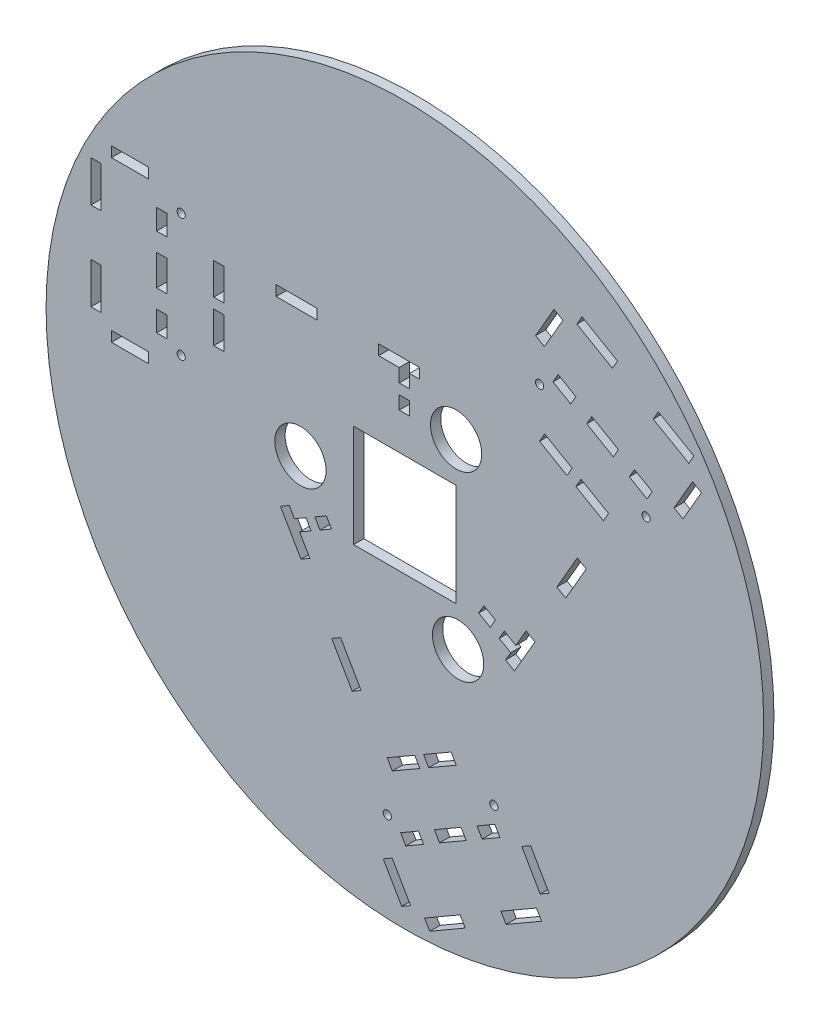
SolidWorks part; units mm, degrees
material "Balsa"
ref_plane "Plan de face" through (0, 0, 0) normal (0, 0, 1) x (1, 0, 0)
ref_plane "Plan de dessus" through (0, 0, 0) normal (0, 1, 0) x (1, 0, 0)
ref_plane "Plan de droite" through (0, 0, 0) normal (1, 0, 0) x (0, 0, -1)
sketch "Esquisse1" plane through (0, 0, 0) normal (0, 0, 1) x (1, 0, 0)
  circle A0 centre (148.0804, -12.1102) radius 175
  dimension "D1" = 350
extrude "Boss.-Extru.1" add sketch "Esquisse1" along normal blind 5
sketch "Esquisse2" plane through (0, 0, 5) normal (0, 0, 1) x (1, 0, 0)
  line L0 (135.3118, 53.7774) -> (135.3118, 48.7774)
  line L1 (5, 72.2774) -> (23, 72.2774)
  line L2 (5, 72.2774) -> (5, 67.2774)
  line L3 (5, 67.2774) -> (23, 67.2774)
  line L4 (23, 72.2774) -> (23, 67.2774)
  line L5 (-5, 62.2774) -> (0, 62.2774)
  line L6 (-5, 62.2774) -> (-5, 42.2774)
  line L7 (-5, 42.2774) -> (0, 42.2774)
  line L8 (0, 62.2774) -> (0, 42.2774)
  line L9 (-5, 19.2774) -> (0, 19.2774)
  line L10 (-5, 19.2774) -> (-5, -0.7226)
  line L11 (-5, -0.7226) -> (0, -0.7226)
  line L12 (0, 19.2774) -> (0, -0.7226)
  line L13 (5, -5.7226) -> (23, -5.7226)
  line L14 (5, -5.7226) -> (5, -10.7226)
  line L15 (5, -10.7226) -> (23, -10.7226)
  line L16 (23, -5.7226) -> (23, -10.7226)
  line L17 (27, 14.2774) -> (32, 14.2774)
  line L18 (27, 14.2774) -> (27, 4.2774)
  line L19 (27, 4.2774) -> (32, 4.2774)
  line L20 (32, 14.2774) -> (32, 4.2774)
  line L21 (27, 38.2774) -> (32, 38.2774)
  line L22 (27, 38.2774) -> (27, 23.2774)
  line L23 (27, 23.2774) -> (32, 23.2774)
  line L24 (32, 38.2774) -> (32, 23.2774)
  line L25 (27, 57.2774) -> (32, 57.2774)
  line L26 (27, 57.2774) -> (27, 47.2774)
  line L27 (27, 47.2774) -> (32, 47.2774)
  line L28 (32, 57.2774) -> (32, 47.2774)
  line L29 (54.86, 48.7774) -> (59.86, 48.7774)
  line L30 (54.86, 48.7774) -> (54.86, 33.2774)
  line L31 (54.86, 33.2774) -> (59.86, 33.2774)
  line L32 (59.86, 48.7774) -> (59.86, 33.2774)
  line L33 (54.86, 28.2774) -> (59.86, 28.2774)
  line L34 (54.86, 28.2774) -> (54.86, 12.7774)
  line L35 (54.86, 12.7774) -> (59.86, 12.7774)
  line L36 (59.86, 28.2774) -> (59.86, 12.7774)
  line L37 (85.3118, 53.7774) -> (105.3118, 53.7774)
  line L38 (85.3118, 53.7774) -> (85.3118, 48.7774)
  line L39 (85.3118, 48.7774) -> (105.3118, 48.7774)
  line L40 (105.3118, 53.7774) -> (105.3118, 48.7774)
  line L41 (145.3118, 37.2774) -> (150.3118, 37.2774)
  line L42 (145.3118, 37.2774) -> (145.3118, 30.7774)
  line L43 (145.3118, 30.7774) -> (150.3118, 30.7774)
  line L44 (150.3118, 37.2774) -> (150.3118, 30.7774)
  line L45 (135.3118, 48.7774) -> (145.3118, 48.7774)
  line L46 (155.3118, 48.7774) -> (135.3118, 48.7774) construction
  line L47 (145.3118, 48.7774) -> (145.3118, 42.2774)
  line L48 (145.3118, 42.2774) -> (150.3118, 42.2774)
  line L49 (150.3118, 42.2774) -> (150.3118, 48.7774)
  line L50 (150.3118, 48.7774) -> (155.3118, 48.7774)
  line L51 (155.3118, 48.7774) -> (155.3118, 53.7774)
  line L52 (155.3118, 53.7774) -> (135.3118, 53.7774)
  line L53 (292.7025, 69.6073) -> (283.7025, 54.0188)
  line L54 (292.7025, 69.6073) -> (288.3723, 72.1073)
  line L55 (288.3723, 72.1073) -> (279.3723, 56.5188)
  line L56 (283.7025, 54.0188) -> (279.3723, 56.5188)
  line L57 (289.0422, 83.2676) -> (286.5422, 78.9374)
  line L58 (289.0422, 83.2676) -> (271.7217, 93.2676)
  line L59 (271.7217, 93.2676) -> (269.2217, 88.9374)
  line L60 (286.5422, 78.9374) -> (269.2217, 88.9374)
  line L61 (251.8031, 104.7676) -> (249.3031, 100.4374)
  line L62 (251.8031, 104.7676) -> (234.4826, 114.7676)
  line L63 (234.4826, 114.7676) -> (231.9826, 110.4374)
  line L64 (249.3031, 100.4374) -> (231.9826, 110.4374)
  line L65 (225.1525, 108.6073) -> (216.1525, 93.0188)
  line L66 (225.1525, 108.6073) -> (220.8223, 111.1073)
  line L67 (220.8223, 111.1073) -> (211.8223, 95.5188)
  line L68 (216.1525, 93.0188) -> (211.8223, 95.5188)
  line L69 (231.473, 79.5547) -> (228.973, 75.2246)
  line L70 (231.473, 79.5547) -> (222.8127, 84.5547)
  line L71 (222.8127, 84.5547) -> (220.3127, 80.2246)
  line L72 (228.973, 75.2246) -> (220.3127, 80.2246)
  line L73 (252.2576, 67.5547) -> (249.7576, 63.2246)
  line L74 (252.2576, 67.5547) -> (239.2672, 75.0547)
  line L75 (239.2672, 75.0547) -> (236.7672, 70.7246)
  line L76 (249.7576, 63.2246) -> (236.7672, 70.7246)
  line L77 (268.7121, 58.0547) -> (266.2121, 53.7246)
  line L78 (268.7121, 58.0547) -> (260.0518, 63.0547)
  line L79 (260.0518, 63.0547) -> (257.5518, 58.7246)
  line L80 (266.2121, 53.7246) -> (257.5518, 58.7246)
  line L81 (247.4209, 38.1773) -> (244.9209, 33.8472)
  line L82 (247.4209, 38.1773) -> (233.9975, 45.9273)
  line L83 (233.9975, 45.9273) -> (231.4975, 41.5972)
  line L84 (244.9209, 33.8472) -> (231.4975, 41.5972)
  line L85 (229.6673, 48.4273) -> (227.1673, 44.0972)
  line L86 (229.6673, 48.4273) -> (216.2439, 56.1773)
  line L87 (216.2439, 56.1773) -> (213.7439, 51.8472)
  line L88 (227.1673, 44.0972) -> (213.7439, 51.8472)
  line L89 (211.5251, -33.996) -> (207.195, -31.496)
  line L90 (236.5251, 9.3053) -> (226.5251, -8.0153)
  line L91 (236.5251, 9.3053) -> (232.195, 11.8053)
  line L92 (232.195, 11.8053) -> (222.195, -5.5153)
  line L93 (226.5251, -8.0153) -> (222.195, -5.5153)
  line L94 (192.2357, -34.4063) -> (189.7357, -38.7364)
  line L95 (192.2357, -34.4063) -> (186.6065, -31.1563)
  line L96 (186.6065, -31.1563) -> (184.1065, -35.4864)
  line L97 (189.7357, -38.7364) -> (184.1065, -35.4864)
  line L98 (207.195, -31.496) -> (202.195, -40.1563)
  line L99 (202.195, -40.1563) -> (196.5658, -36.9063)
  line L100 (196.5658, -36.9063) -> (194.0658, -41.2364)
  line L101 (194.0658, -41.2364) -> (199.695, -44.4864)
  line L102 (199.695, -44.4864) -> (197.195, -48.8165)
  line L103 (197.195, -48.8165) -> (201.5251, -51.3165)
  line L104 (201.5251, -51.3165) -> (211.5251, -33.996)
  line L105 (146.5388, -178.2153) -> (137.5388, -162.6268)
  line L106 (146.5388, -178.2153) -> (150.869, -175.7153)
  line L107 (150.869, -175.7153) -> (141.869, -160.1268)
  line L108 (137.5388, -162.6268) -> (141.869, -160.1268)
  line L109 (160.1991, -181.8755) -> (157.6991, -177.5454)
  line L110 (160.1991, -181.8755) -> (177.5196, -171.8755)
  line L111 (177.5196, -171.8755) -> (175.0196, -167.5454)
  line L112 (157.6991, -177.5454) -> (175.0196, -167.5454)
  line L113 (197.4382, -160.3755) -> (194.9382, -156.0454)
  line L114 (197.4382, -160.3755) -> (214.7587, -150.3755)
  line L115 (214.7587, -150.3755) -> (212.2587, -146.0454)
  line L116 (194.9382, -156.0454) -> (212.2587, -146.0454)
  line L117 (214.0888, -139.2153) -> (205.0888, -123.6268)
  line L118 (214.0888, -139.2153) -> (218.4189, -136.7153)
  line L119 (218.4189, -136.7153) -> (209.4189, -121.1268)
  line L120 (205.0888, -123.6268) -> (209.4189, -121.1268)
  line L121 (185.7683, -130.1627) -> (183.2683, -125.8326)
  line L122 (185.7683, -130.1627) -> (194.4286, -125.1627)
  line L123 (194.4286, -125.1627) -> (191.9286, -120.8326)
  line L124 (183.2683, -125.8326) -> (191.9286, -120.8326)
  line L125 (164.9837, -142.1627) -> (162.4837, -137.8326)
  line L126 (164.9837, -142.1627) -> (177.9741, -134.6627)
  line L127 (177.9741, -134.6627) -> (175.4741, -130.3326)
  line L128 (162.4837, -137.8326) -> (175.4741, -130.3326)
  line L129 (148.5292, -151.6627) -> (146.0292, -147.3326)
  line L130 (148.5292, -151.6627) -> (157.1895, -146.6627)
  line L131 (157.1895, -146.6627) -> (154.6895, -142.3326)
  line L132 (146.0292, -147.3326) -> (154.6895, -142.3326)
  line L133 (141.9604, -123.2852) -> (139.4604, -118.9551)
  line L134 (141.9604, -123.2852) -> (155.3838, -115.5352)
  line L135 (155.3838, -115.5352) -> (152.8838, -111.2051)
  line L136 (139.4604, -118.9551) -> (152.8838, -111.2051)
  line L137 (159.7139, -113.0352) -> (157.2139, -108.7051)
  line L138 (159.7139, -113.0352) -> (173.1373, -105.2852)
  line L139 (173.1373, -105.2852) -> (170.6373, -100.9551)
  line L140 (157.2139, -108.7051) -> (170.6373, -100.9551)
  line L141 (97.4044, -56.1119) -> (101.7345, -53.6119)
  line L142 (122.4044, -99.4132) -> (112.4044, -82.0927)
  line L143 (122.4044, -99.4132) -> (126.7345, -96.9132)
  line L144 (126.7345, -96.9132) -> (116.7345, -79.5927)
  line L145 (112.4044, -82.0927) -> (116.7345, -79.5927)
  line L146 (106.6938, -39.2017) -> (104.1938, -34.8716)
  line L147 (106.6938, -39.2017) -> (112.323, -35.9517)
  line L148 (112.323, -35.9517) -> (109.823, -31.6216)
  line L149 (104.1938, -34.8716) -> (109.823, -31.6216)
  line L150 (101.7345, -53.6119) -> (96.7345, -44.9517)
  line L151 (96.7345, -44.9517) -> (102.3637, -41.7017)
  line L152 (102.3637, -41.7017) -> (99.8637, -37.3716)
  line L153 (99.8637, -37.3716) -> (94.2345, -40.6216)
  line L154 (94.2345, -40.6216) -> (91.7345, -36.2914)
  line L155 (91.7345, -36.2914) -> (87.4044, -38.7914)
  line L156 (87.4044, -38.7914) -> (97.4044, -56.1119)
  line L157 (135.3118, 53.7774) -> (135.3118, 48.7774) construction
  line L158 (105.3118, 53.7774) -> (135.3118, 53.7774) construction
  point P83 (148.0804, -12.1102)
  point P192 (148.0804, -12.1102)
  point P193 (148.0804, -12.1102)
  dimension "D1" = 3
extrude "Enlèv. mat.-Extru.1" cut sketch "Esquisse2" against normal blind 5
sketch "Esquisse6" plane through (0, 0, 5) normal (0, 0, 1) x (1, 0, 0)
  line L0 (93.9998, -7.2151) -> (100.2998, -18.127) construction
  line L2 (123.0804, -37.1102) -> (173.0804, -37.1102)
  line L3 (123.0804, -37.1102) -> (123.0804, 12.8898)
  line L4 (123.0804, 12.8898) -> (173.0804, 12.8898)
  line L5 (173.0804, -37.1102) -> (173.0804, 12.8898)
  line L6 (123.0804, -37.1102) -> (173.0804, 12.8898) construction
  line L7 (123.0804, 12.8898) -> (173.0804, -37.1102) construction
  circle A0 centre (173.06, 32.2774) radius 12.5
  circle A1 centre (174.0314, -55.9369) radius 12.5
  circle A2 centre (97.1498, -12.671) radius 12.5
  point P2 (148.0804, -12.1102)
  point P8 (148.0804, -12.1102)
  point P10 (148.0804, -12.1102)
  dimension "D2" = 25
  dimension "D3" = 50
  dimension "D4" = 50
  dimension "D1" = 3
extrude "Enlèv. mat.-Extru.6" cut sketch "Esquisse6" against normal blind 5
hole_wizard "Trous de centrage Ø4.0mm1" positions "Esquisse8" profile "Esquisse9" hole size "Ø4.0" standard "Ansi Metric" end condition through all
sketch "Esquisse8" plane through (148.0804, -12.1102, -78) normal (0, 0, -1) x (1, 0, 0)
  point P0 (65.7012, -88.0226)
  point P3 (117.6627, -58.0226)
  point P6 (-109.0804, -72.8876)
  point P9 (-109.0804, -12.8876)
  point P12 (-8.5823, 130.9102)
  point P15 (43.3792, 100.9102)
sketch "Esquisse9" plane through (213.7816, 75.9124, -78) normal (1, 0, 0) x (0, 1, 0)
  line L0 (0, 0) -> (0, 83)
  line L1 (0, 83) -> (2, 83)
  line L2 (2, 83) -> (2, 0)
  line L3 (2, 0) -> (0, 0)
  line L4 (0, -6.35) -> (0, 107.95) construction
  dimension "Diamètre du perçage jusqu'au prochain" = 4
  dimension "Profondeur du perçage jusqu'au prochain" = 83
